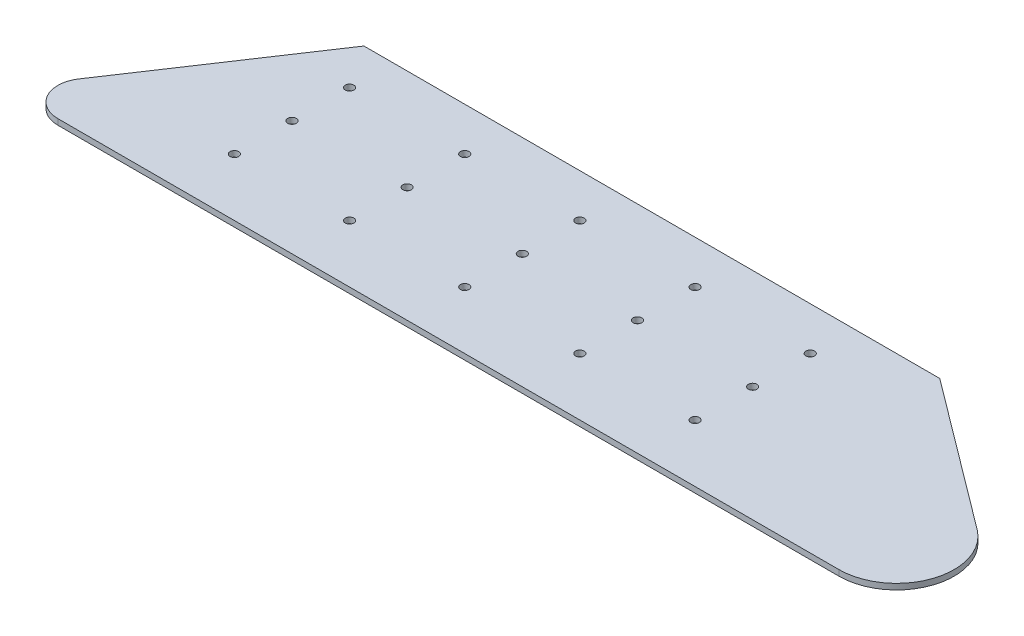
SolidWorks part; units mm, degrees
ref_plane "Front Plane" through (0, 0, 0) normal (0, 0, 1) x (1, 0, 0)
ref_plane "Top Plane" through (0, 0, 0) normal (0, 1, 0) x (1, 0, 0)
ref_plane "Right Plane" through (0, 0, 0) normal (1, 0, 0) x (0, 0, -1)
sketch "Sketch1" plane through (0, 0, 0) normal (0, 1, 0) x (1, 0, 0)
  line L0 (-17.984, 0) -> (332.016, 0)
  line L1 (-266.7276, 0) -> (266.7276, 0) construction
  line L2 (332.016, 0) -> (232.016, 75)
  line L3 (232.016, 75) -> (32.016, 75)
  line L4 (32.016, 75) -> (-17.984, 0)
  line L5 (-45.5557, 20) -> (439.4037, 20) construction
  line L6 (-34.9172, 40) -> (434.9926, 40) construction
  line L7 (-27.9699, 60) -> (319.174, 60) construction
  circle A0 centre (42.016, 20) radius 1.5
  circle A1 centre (82.016, 20) radius 1.5
  circle A2 centre (122.016, 20) radius 1.5
  circle A3 centre (162.016, 20) radius 1.5
  circle A4 centre (202.016, 20) radius 1.5
  circle A5 centre (42.016, 40) radius 1.5
  circle A6 centre (82.016, 40) radius 1.5
  circle A7 centre (122.016, 40) radius 1.5
  circle A8 centre (162.016, 40) radius 1.5
  circle A9 centre (202.016, 40) radius 1.5
  circle A10 centre (202.016, 60) radius 1.5
  circle A11 centre (162.016, 60) radius 1.5
  circle A12 centre (122.016, 60) radius 1.5
  circle A13 centre (82.016, 60) radius 1.5
  circle A14 centre (42.016, 60) radius 1.5
  dimension "D13" = 3
  dimension "D14" = 3
  dimension "D15" = 3
  dimension "D16" = 3
  dimension "D17" = 3
  dimension "D18" = 3
  dimension "D19" = 3
  dimension "D20" = 3
  dimension "D21" = 3
  dimension "D22" = 3
  dimension "D23" = 3
  dimension "D24" = 3
  dimension "D25" = 3
  dimension "D26" = 3
  dimension "D27" = 3
  dimension "D1" = 350
  dimension "D2" = 75
  dimension "D3" = 100
  dimension "D4" = 200
  dimension "D5" = 20
  dimension "D6" = 40
  dimension "D7" = 60
  dimension "D8" = 60
  dimension "D9" = 100
  dimension "D10" = 140
  dimension "D11" = 180
  dimension "D12" = 220
extrude "Boss-Extrude1" add sketch "Sketch1" along normal blind 2
fillet "Fillet4" radius 20 1 edges at (332.016, 1, 0)
fillet "Fillet5" radius 10 1 edges at (-17.984, 1, 0)
